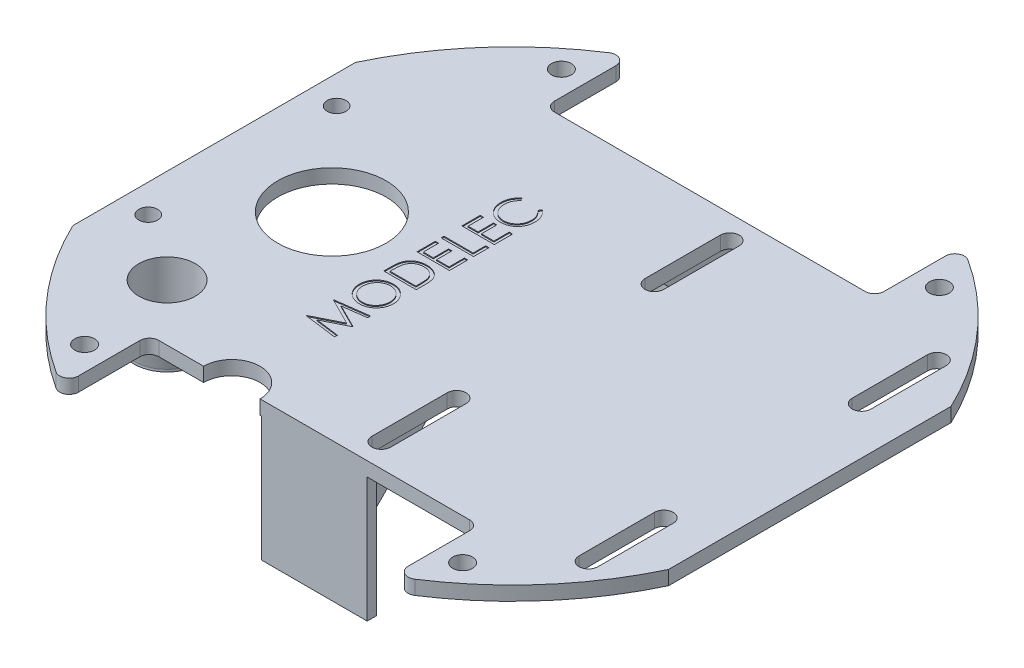
SolidWorks part; units mm, degrees
ref_plane "Plan de face" through (0, 0, 0) normal (0, 0, 1) x (1, 0, 0)
ref_plane "Plan de dessus" through (0, 0, 0) normal (0, 1, 0) x (1, 0, 0)
ref_plane "Plan de droite" through (0, 0, 0) normal (1, 0, 0) x (0, 0, -1)
sketch "Esquisse1" plane through (0, 0, 0) normal (0, 1, 0) x (1, 0, 0)
  line L0 (0, 83.5544) -> (0, -91.5756) construction
  line L1 (-140.3714, 0) -> (145.9862, 0) construction
  line L2 (35, 42) -> (-35, 42)
  line L3 (-35, 42) -> (-35, 60.6218)
  line L4 (-63.2456, -30) -> (-63.2456, 30)
  line L5 (-37, 57.0526) -> (-37, 42) construction
  line L6 (-46.4527, 49.6603) -> (-37, 45.0526) construction
  line L7 (-41.7264, 47.3565) -> (-37, 57.0526) construction
  line L8 (-35, 60.6218) -> (-65.5835, 60.6218) construction
  line L9 (-35, -42) -> (-35, -60.6218)
  line L10 (35, -42) -> (-35, -42)
  line L11 (35, 42) -> (35, 60.6218)
  line L12 (63.2456, -30) -> (63.2456, 30)
  line L13 (35, -42) -> (35, -60.6218)
  line L14 (9.2456, 37) -> (9.2456, 21) construction
  line L17 (31.2456, 0) -> (31.2456, 33.6619) construction
  line L18 (11.2456, 37) -> (11.2456, 21)
  line L21 (7.2456, 37) -> (7.2456, 21)
  line L24 (9.2456, -21) -> (9.2456, -37) construction
  line L27 (11.2456, -21) -> (11.2456, -37)
  line L28 (7.2456, -21) -> (7.2456, -37)
  line L29 (53.2456, -21) -> (53.2456, -37) construction
  line L30 (51.2456, -21) -> (51.2456, -37)
  line L31 (55.2456, -21) -> (55.2456, -37)
  line L32 (53.2456, 37) -> (53.2456, 21) construction
  line L33 (51.2456, 37) -> (51.2456, 21)
  line L34 (55.2456, 37) -> (55.2456, 21)
  circle A0 centre (0, 0) radius 70 construction
  arc A1 (-63.2456, 30) -> (-35, 60.6218) centre (0, 0) cw
  circle A2 centre (0, 0) radius 68 construction
  arc A3 (-46.4527, 49.6603) -> (-37, 45.0526) centre (-37, 57.0526) ccw construction
  circle A4 centre (-40.1347, 50.6218) radius 2.1
  circle A5 centre (-40.1347, -50.6218) radius 2.1
  arc A6 (-63.2456, -30) -> (-35, -60.6218) centre (0, 0) ccw
  circle A7 centre (40.1347, 50.6218) radius 2.1
  arc A8 (63.2456, 30) -> (35, 60.6218) centre (0, 0) ccw
  circle A9 centre (40.1347, -50.6218) radius 2.1
  arc A10 (63.2456, -30) -> (35, -60.6218) centre (0, 0) cw
  circle A11 centre (-38.2456, 0) radius 11.5
  arc A20 (11.2456, 37) -> (7.2456, 37) centre (9.2456, 37) ccw
  arc A21 (7.2456, 21) -> (11.2456, 21) centre (9.2456, 21) ccw
  arc A22 (11.2456, -21) -> (7.2456, -21) centre (9.2456, -21) ccw
  arc A23 (7.2456, -37) -> (11.2456, -37) centre (9.2456, -37) ccw
  arc A24 (51.2456, -21) -> (55.2456, -21) centre (53.2456, -21) cw
  arc A25 (55.2456, -37) -> (51.2456, -37) centre (53.2456, -37) cw
  arc A26 (51.2456, 37) -> (55.2456, 37) centre (53.2456, 37) cw
  arc A27 (55.2456, 21) -> (51.2456, 21) centre (53.2456, 21) cw
  arc A28 (-23.5, 42) -> (-11.5, 42) centre (-17.5, 42) ccw
  arc A29 (-23.5, -42) -> (-11.5, -42) centre (-17.5, -42) cw
  point P28 (-63.2456, 0)
  point P34 (0, 42)
  point P39 (0, -42)
  point P41 (9.2456, 29)
  point P49 (9.2456, -29)
  point P57 (53.2456, -29)
  point P64 (53.2456, 29)
  dimension "D1" = 140
  dimension "D2" = 42
  dimension "D5" = 136
  dimension "D7" = 12
  dimension "D8" = 4.2
  dimension "D10" = 23
  dimension "D17" = 6
  dimension "D3" = 35
  dimension "D4" = 30
  dimension "D6" = 2
  dimension "D9" = 10
  dimension "D11" = 25
  dimension "D12" = 16
  dimension "D13" = 58
  dimension "D14" = 44
  dimension "D15" = 4
  dimension "D16" = 10
  dimension "D18" = 17.5
extrude "Boss.-Extru.1" add sketch "Esquisse1" along normal blind 3 contours A28 L2 L3 A1 L4 A6 L9 L10 L13 A10 L12 A8 L11 A23 L28 A22 L27 A21 L21 A20 L18 A11 A9 A5 A4 A7 L31 A25 L30 A24 L34 A27 L33 A26 | L2 A28 region at (0.7933, 0, 0) region at (-17.5, 0, -39.4535)
fillet "Congé1" radius 2 8 edges at (35, 1.5, -42) (35, 1.5, -60.6218) (-35, 1.5, -60.6218) (-35, 1.5, -42) (35, 1.5, 42) (35, 1.5, 60.6218) (-35, 1.5, 42) (-35, 1.5, 60.6218)
sketch "Esquisse5" plane through (0, 0, 0) normal (0, -1, 0) x (1, 0, 0)
  line L0 (-72.6895, 0) -> (107.3438, 0) construction
  line L1 (11.25, 42) -> (11.25, 40)
  line L2 (11.25, 40) -> (-11.25, 40)
  line L3 (-11.25, 40) -> (-11.25, 42)
  line L4 (0, 57.0526) -> (0, -69.7312) construction
  line L5 (11.25, -42) -> (11.25, -40)
  line L6 (11.25, -40) -> (-11.25, -40)
  line L7 (-11.25, -40) -> (-11.25, -42)
  line L9 (35, -44) -> (35, -57.0526)
  line L10 (63.2456, -30) -> (63.2456, 30)
  line L11 (35, 57.0526) -> (35, 44)
  line L12 (33, 42) -> (-11.5, 42)
  line L13 (-35, 44) -> (-35, 57.0526)
  line L14 (-63.2456, 30) -> (-63.2456, -30)
  line L15 (-35, -57.0526) -> (-35, -44)
  line L16 (-33, -42) -> (33, -42)
  line L18 (35, -44) -> (35, -57.0526)
  line L19 (63.2456, -30) -> (63.2456, 30)
  line L20 (35, 57.0526) -> (35, 44)
  line L21 (33, 42) -> (-11.5, 42)
  line L22 (-35, 44) -> (-35, 57.0526)
  line L23 (-63.2456, 30) -> (-63.2456, -30)
  line L24 (-35, -57.0526) -> (-35, -44)
  line L25 (-33, -42) -> (33, -42)
  line L36 (-23.5, 42) -> (-33, 42)
  line L37 (-23.5, 42) -> (-33, 42)
  arc A13 (35, -57.0526) -> (38.0882, -58.7306) centre (37, -57.0526) ccw
  arc A14 (38.0882, -58.7306) -> (63.2456, -30) centre (0, 0) ccw
  arc A15 (63.2456, 30) -> (38.0882, 58.7306) centre (0, 0) ccw
  arc A16 (38.0882, 58.7306) -> (35, 57.0526) centre (37, 57.0526) ccw
  arc A17 (33, 42) -> (35, 44) centre (33, 44) ccw
  arc A18 (-35, 44) -> (-33, 42) centre (-33, 44) ccw
  arc A19 (-35, 57.0526) -> (-38.0882, 58.7306) centre (-37, 57.0526) ccw
  arc A20 (-38.0882, 58.7306) -> (-63.2456, 30) centre (0, 0) ccw
  arc A21 (-63.2456, -30) -> (-38.0882, -58.7306) centre (0, 0) ccw
  arc A22 (-38.0882, -58.7306) -> (-35, -57.0526) centre (-37, -57.0526) ccw
  arc A23 (-33, -42) -> (-35, -44) centre (-33, -44) ccw
  arc A25 (35, -44) -> (33, -42) centre (33, -44) ccw
  arc A26 (35, -57.0526) -> (38.0882, -58.7306) centre (37, -57.0526) ccw
  arc A27 (38.0882, -58.7306) -> (63.2456, -30) centre (0, 0) ccw
  arc A28 (63.2456, 30) -> (38.0882, 58.7306) centre (0, 0) ccw
  arc A29 (38.0882, 58.7306) -> (35, 57.0526) centre (37, 57.0526) ccw
  arc A30 (33, 42) -> (35, 44) centre (33, 44) ccw
  arc A31 (-35, 44) -> (-33, 42) centre (-33, 44) ccw
  arc A32 (-35, 57.0526) -> (-38.0882, 58.7306) centre (-37, 57.0526) ccw
  arc A33 (-38.0882, 58.7306) -> (-63.2456, 30) centre (0, 0) ccw
  arc A34 (-63.2456, -30) -> (-38.0882, -58.7306) centre (0, 0) ccw
  arc A35 (-38.0882, -58.7306) -> (-35, -57.0526) centre (-37, -57.0526) ccw
  arc A36 (-33, -42) -> (-35, -44) centre (-33, -44) ccw
  arc A38 (35, -44) -> (33, -42) centre (33, -44) ccw
  arc A40 (-23.5, 42) -> (-11.5, 42) centre (-17.5, 42) ccw
  arc A41 (-23.5, 42) -> (-11.5, 42) centre (-17.5, 42) ccw
  line M36 (33, 42) -> (-11.5, 42)
  line M48 (-33, -42) -> (33, -42)
  dimension "D2" = 2
  dimension "D3" = 22.5
  dimension "D1" = 0
extrude "Boss.-Extru.2" add sketch "Esquisse5" along normal blind 26.5 contours L3 L2 L1 M36 | L6 L7 L5 M48 region at (0, 0, 41) region at (0, 0, -41)
sketch "Esquisse6" plane through (0, 0, 40) normal (0, 0, -1) x (-1, 0, 0)
  line L0 (-7, 0) -> (-7, -15)
  line L1 (-7, -15) -> (-4, -15)
  line L2 (-4, -15) -> (-4, 0)
  line L3 (0, 8.5664) -> (0, -28.8137) construction
  line L4 (11.25, 0) -> (-11.25, 0)
  line L5 (-11.25, 0) -> (-11.25, -26.5)
  line L6 (-11.25, -26.5) -> (11.25, -26.5)
  line L7 (11.25, -26.5) -> (11.25, 0)
  line L8 (11.25, 0) -> (-11.25, 0)
  line L9 (-11.25, 0) -> (-11.25, -26.5)
  line L10 (-11.25, -26.5) -> (11.25, -26.5)
  line L11 (11.25, -26.5) -> (11.25, 0)
  line L12 (4, -15) -> (4, 0)
  line L13 (7, -15) -> (4, -15)
  line L14 (7, 0) -> (7, -15)
  line M9 (11.25, 0) -> (-11.25, 0)
  dimension "D2" = 3
  dimension "D3" = 15
  dimension "D4" = 4
  dimension "D1" = 0
extrude "Boss.-Extru.3" add sketch "Esquisse6" along normal blind 15 contours L14 L8 L12 L13 | L1 L2 L0 M9 region at (5.5, -7.5, 40) region at (-5.5, -7.5, 40)
chamfer "Chanfrein1" distance 15 angle 45 2 edges at (-5.5, -15, 25) (5.5, -15, 25)
mirror "Symétrie3" about plane through (0, 0, 0) normal (0, 0, 1) of "Chanfrein1", "Boss.-Extru.3"
sketch "Esquisse7" plane through (0, 3, 0) normal (0, 1, 0) x (1, 0, 0)
  line L0 (-15, 42) -> (-15, -42) construction
  line L1 (33, 42) -> (-33, 42) construction
  line L2 (33, -42) -> (-11.5, -42) construction
  text T0 "MODELEC" font "Century Gothic" height in points 26
  dimension "D1" = 15
extrude "Enlèv. mat.-Extru.2" cut sketch "Esquisse7" against normal blind 0.2
sketch "Esquisse8" plane through (0, 3, 0) normal (0, 1, 0) x (1, 0, 0)
  line L0 (-63.2456, 0) -> (63.2456, 0) construction
  line L9 (35, 57.0526) -> (35, 44)
  line L10 (33, 42) -> (-33, 42)
  line L11 (-35, 44) -> (-35, 57.0526)
  line L12 (-63.2456, 30) -> (-63.2456, -30)
  line L13 (-35, -57.0526) -> (-35, -44)
  line L14 (-33, -42) -> (-23.5, -42)
  line L15 (-11.5, -42) -> (33, -42)
  line L16 (35, -44) -> (35, -57.0526)
  line L17 (63.2456, -30) -> (63.2456, 30)
  line L18 (35, 57.0526) -> (35, 44)
  line L19 (33, 42) -> (-33, 42)
  line L20 (-35, 44) -> (-35, 57.0526)
  line L21 (-63.2456, 30) -> (-63.2456, -30)
  line L22 (-35, -57.0526) -> (-35, -44)
  line L23 (-33, -42) -> (-23.5, -42)
  line L24 (-11.5, -42) -> (33, -42)
  line L25 (35, -44) -> (35, -57.0526)
  line L26 (63.2456, -30) -> (63.2456, 30)
  circle A0 centre (-43.2456, -30) radius 6
  arc A13 (63.2456, 30) -> (38.0882, 58.7306) centre (0, 0) ccw
  arc A14 (38.0882, 58.7306) -> (35, 57.0526) centre (37, 57.0526) ccw
  arc A15 (33, 42) -> (35, 44) centre (33, 44) ccw
  arc A16 (-35, 44) -> (-33, 42) centre (-33, 44) ccw
  arc A17 (-35, 57.0526) -> (-38.0882, 58.7306) centre (-37, 57.0526) ccw
  arc A18 (-38.0882, 58.7306) -> (-63.2456, 30) centre (0, 0) ccw
  arc A19 (-63.2456, -30) -> (-38.0882, -58.7306) centre (0, 0) ccw
  arc A20 (-38.0882, -58.7306) -> (-35, -57.0526) centre (-37, -57.0526) ccw
  arc A21 (-33, -42) -> (-35, -44) centre (-33, -44) ccw
  arc A22 (-11.5, -42) -> (-23.5, -42) centre (-17.5, -42) ccw
  arc A23 (35, -44) -> (33, -42) centre (33, -44) ccw
  arc A24 (35, -57.0526) -> (38.0882, -58.7306) centre (37, -57.0526) ccw
  arc A25 (38.0882, -58.7306) -> (63.2456, -30) centre (0, 0) ccw
  arc A26 (63.2456, 30) -> (38.0882, 58.7306) centre (0, 0) ccw
  arc A27 (38.0882, 58.7306) -> (35, 57.0526) centre (37, 57.0526) ccw
  arc A28 (33, 42) -> (35, 44) centre (33, 44) ccw
  arc A29 (-35, 44) -> (-33, 42) centre (-33, 44) ccw
  arc A30 (-35, 57.0526) -> (-38.0882, 58.7306) centre (-37, 57.0526) ccw
  arc A31 (-38.0882, 58.7306) -> (-63.2456, 30) centre (0, 0) ccw
  arc A32 (-63.2456, -30) -> (-38.0882, -58.7306) centre (0, 0) ccw
  arc A33 (-38.0882, -58.7306) -> (-35, -57.0526) centre (-37, -57.0526) ccw
  arc A34 (-33, -42) -> (-35, -44) centre (-33, -44) ccw
  arc A35 (-11.5, -42) -> (-23.5, -42) centre (-17.5, -42) ccw
  arc A36 (35, -44) -> (33, -42) centre (33, -44) ccw
  arc A37 (35, -57.0526) -> (38.0882, -58.7306) centre (37, -57.0526) ccw
  arc A38 (38.0882, -58.7306) -> (63.2456, -30) centre (0, 0) ccw
  dimension "D2" = 12
  dimension "D3" = 20
  dimension "D4" = 30
  dimension "D1" = 0
extrude "Enlèv. mat.-Extru.3" cut sketch "Esquisse8" against normal through all flip side to cut
sketch "Esquisse9" plane through (0, 0, 0) normal (0, -1, 0) x (1, 0, 0)
  circle A0 centre (-43.2456, 30) radius 6 construction
  circle A1 centre (-43.2456, 30) radius 6
  circle A2 centre (-43.2456, 30) radius 7
  dimension "D1" = 14
  dimension "D2" = 12
extrude "Boss.-Extru.4" add sketch "Esquisse9" along normal blind 9
chamfer "Chanfrein2" distance 1.5 angle 80 1 edges at (-43.2456, 0, 37) first distance on face at (-0.7609, 0, 1.6957)
sketch "Esquisse10" plane through (0, 3, 0) normal (0, 1, 0) x (1, 0, 0)
  line L0 (-63.2456, 0) -> (63.2456, 0) construction
  line L9 (35, 57.0526) -> (35, 44)
  line L10 (33, 42) -> (-33, 42)
  line L11 (-35, 44) -> (-35, 57.0526)
  line L12 (-63.2456, 30) -> (-63.2456, -30)
  line L13 (-35, -57.0526) -> (-35, -44)
  line L14 (-33, -42) -> (-23.5, -42)
  line L15 (-11.5, -42) -> (33, -42)
  line L16 (35, -44) -> (35, -57.0526)
  line L17 (63.2456, -30) -> (63.2456, 30)
  line L18 (35, 57.0526) -> (35, 44)
  line L19 (33, 42) -> (-33, 42)
  line L20 (-35, 44) -> (-35, 57.0526)
  line L21 (-63.2456, 30) -> (-63.2456, -30)
  line L22 (-35, -57.0526) -> (-35, -44)
  line L23 (-33, -42) -> (-23.5, -42)
  line L24 (-11.5, -42) -> (33, -42)
  line L25 (35, -44) -> (35, -57.0526)
  line L26 (63.2456, -30) -> (63.2456, 30)
  circle A0 centre (-57.2456, 20) radius 2
  circle A1 centre (-57.2456, -20) radius 2
  arc A13 (63.2456, 30) -> (38.0882, 58.7306) centre (0, 0) ccw
  arc A14 (38.0882, 58.7306) -> (35, 57.0526) centre (37, 57.0526) ccw
  arc A15 (33, 42) -> (35, 44) centre (33, 44) ccw
  arc A16 (-35, 44) -> (-33, 42) centre (-33, 44) ccw
  arc A17 (-35, 57.0526) -> (-38.0882, 58.7306) centre (-37, 57.0526) ccw
  arc A18 (-38.0882, 58.7306) -> (-63.2456, 30) centre (0, 0) ccw
  arc A19 (-63.2456, -30) -> (-38.0882, -58.7306) centre (0, 0) ccw
  arc A20 (-38.0882, -58.7306) -> (-35, -57.0526) centre (-37, -57.0526) ccw
  arc A21 (-33, -42) -> (-35, -44) centre (-33, -44) ccw
  arc A22 (-11.5, -42) -> (-23.5, -42) centre (-17.5, -42) ccw
  arc A23 (35, -44) -> (33, -42) centre (33, -44) ccw
  arc A24 (35, -57.0526) -> (38.0882, -58.7306) centre (37, -57.0526) ccw
  arc A25 (38.0882, -58.7306) -> (63.2456, -30) centre (0, 0) ccw
  arc A26 (63.2456, 30) -> (38.0882, 58.7306) centre (0, 0) ccw
  arc A27 (38.0882, 58.7306) -> (35, 57.0526) centre (37, 57.0526) ccw
  arc A28 (33, 42) -> (35, 44) centre (33, 44) ccw
  arc A29 (-35, 44) -> (-33, 42) centre (-33, 44) ccw
  arc A30 (-35, 57.0526) -> (-38.0882, 58.7306) centre (-37, 57.0526) ccw
  arc A31 (-38.0882, 58.7306) -> (-63.2456, 30) centre (0, 0) ccw
  arc A32 (-63.2456, -30) -> (-38.0882, -58.7306) centre (0, 0) ccw
  arc A33 (-38.0882, -58.7306) -> (-35, -57.0526) centre (-37, -57.0526) ccw
  arc A34 (-33, -42) -> (-35, -44) centre (-33, -44) ccw
  arc A35 (-11.5, -42) -> (-23.5, -42) centre (-17.5, -42) ccw
  arc A36 (35, -44) -> (33, -42) centre (33, -44) ccw
  arc A37 (35, -57.0526) -> (38.0882, -58.7306) centre (37, -57.0526) ccw
  arc A38 (38.0882, -58.7306) -> (63.2456, -30) centre (0, 0) ccw
  dimension "D2" = 4
  dimension "D3" = 6
  dimension "D4" = 20
  dimension "D1" = 0
extrude "Enlèv. mat.-Extru.4" cut sketch "Esquisse10" against normal blind 9 flip side to cut
